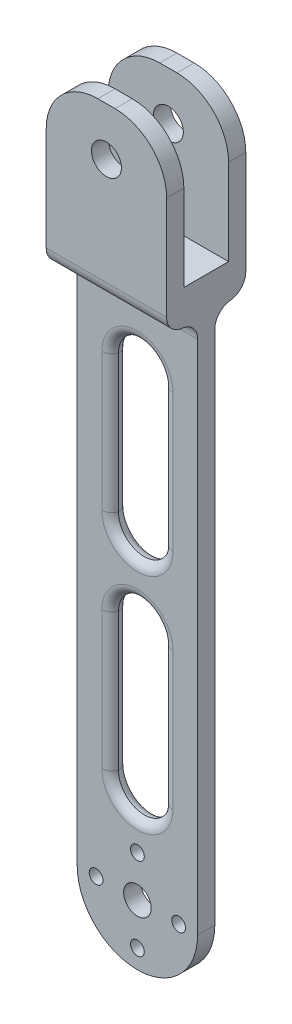
SolidWorks part; units mm, degrees
ref_plane "Front Plane" through (0, 0, 0) normal (0, 0, 1) x (1, 0, 0)
ref_plane "Top Plane" through (0, 0, 0) normal (0, 1, 0) x (1, 0, 0)
ref_plane "Right Plane" through (0, 0, 0) normal (1, 0, 0) x (0, 0, -1)
sketch "Sketch1" plane through (0, 0, 0) normal (0, 0, 1) x (1, 0, 0)
  line L0 (-9.6857, -15) -> (-9.6857, 190)
  line L1 (-9.6857, 190) -> (25.3143, 190)
  line L2 (25.3143, 190) -> (25.3143, -15)
  arc A0 (25.3143, -15) -> (-9.6857, -15) centre (7.8143, -15) cw
  circle A3 centre (19.8143, -15) radius 2
  circle A4 centre (7.8143, -27) radius 2
  circle A5 centre (-4.1857, -15) radius 2
  circle A6 centre (7.8143, -3) radius 2
  point P19 (7.8143, -15)
  dimension "D4" = 4
  dimension "D1" = 205
  dimension "D5" = 12
  dimension "D8" = 35
  dimension "D6" = 4
extrude "Boss-Extrude2" add sketch "Sketch1" along normal blind 5
sketch "Sketch3" plane through (0, 0, 5) normal (0, 0, 1) x (1, 0, 0)
  line L0 (25.3143, -15) -> (25.3143, 190) construction
  line L1 (-9.6857, 190) -> (25.3143, 190)
  line L2 (-9.6857, 190) -> (-9.6857, 140)
  line L3 (-9.6857, 140) -> (25.3143, 140)
  line L4 (25.3143, 190) -> (25.3143, 140)
  dimension "D1" = 50
extrude "Boss-Extrude3" add sketch "Sketch3" along normal blind 9 and the other way blind 14
sketch "Sketch4" plane through (25.3143, 0, 0) normal (1, 0, 0) x (0, 0, -1)
  line L0 (-14, 190) -> (9, 190) construction
  line L1 (-9, 190) -> (4, 190)
  line L2 (-9, 190) -> (-9, 150)
  line L3 (-9, 150) -> (4, 150)
  line L4 (4, 190) -> (4, 150)
  line L5 (-5, 140) -> (-14, 140) construction
  line L6 (-14, 140) -> (-14, 190) construction
  line L7 (9, 140) -> (9, 190) construction
  dimension "D1" = 10
  dimension "D2" = 5
  dimension "D3" = 5
extrude "Cut-Extrude1" cut sketch "Sketch4" against normal through all
sketch "Sketch5" plane through (0, 0, 14) normal (0, 0, 1) x (1, 0, 0)
  line L1 (25.3143, 190) -> (-9.6857, 190) construction
  circle A0 centre (7.8143, 176) radius 4.35
  dimension "D1" = 8.7
  dimension "D2" = 14
extrude "Cut-Extrude2" cut sketch "Sketch5" against normal through all
sketch "Sketch6" plane through (0, 0, 5) normal (0, 0, 1) x (1, 0, 0)
  line L0 (7.8143, 118) -> (7.8143, 78) construction
  line L1 (15.3143, 118) -> (15.3143, 78)
  line L2 (0.3143, 118) -> (0.3143, 78)
  line L4 (-9.6857, 140) -> (-9.6857, -15) construction
  line L5 (25.3143, 140) -> (-9.6857, 140) construction
  line L6 (7.8143, 53) -> (7.8143, 13) construction
  line L7 (15.3143, 53) -> (15.3143, 13)
  line L8 (0.3143, 53) -> (0.3143, 13)
  arc A0 (15.3143, 118) -> (0.3143, 118) centre (7.8143, 118) ccw
  arc A1 (0.3143, 78) -> (15.3143, 78) centre (7.8143, 78) ccw
  arc A2 (15.3143, 53) -> (0.3143, 53) centre (7.8143, 53) ccw
  arc A3 (0.3143, 13) -> (15.3143, 13) centre (7.8143, 13) ccw
  point P2 (7.8143, 98)
  point P13 (7.8143, 33)
  dimension "D5" = 25
  dimension "D1" = 17.5
  dimension "D2" = 22
  dimension "D3" = 40
  dimension "D4" = 15
  dimension "D6" = 40
  dimension "D7" = 15
extrude "Cut-Extrude3" cut sketch "Sketch6" against normal through all
fillet "Fillet14" radius 15 1 edges at (25.3143, 190, 11.5)
fillet "Fillet15" radius 15 1 edges at (-9.6857, 190, 11.5)
fillet "Fillet16" radius 15 1 edges at (-9.6857, 190, -6.5)
fillet "Fillet17" radius 15 1 edges at (25.3143, 190, -6.5)
fillet "Fillet18" radius 5 1 edges at (7.8143, 140, 5)
fillet "Fillet19" radius 5 1 edges at (7.8143, 140, 0)
fillet "Fillet20" radius 5 1 edges at (7.8143, 140, -9)
fillet "Fillet21" radius 5 1 edges at (7.8143, 140, 14)
fillet "Fillet22" radius 3 4 edges at (0.3143, 98, 0) (7.8143, 70.5, 0) (15.3143, 98, 0) (7.8143, 125.5, 0)
fillet "Fillet23" radius 3 4 edges at (15.3143, 98, 5) (7.8143, 70.5, 5) (0.3143, 98, 5) (7.8143, 125.5, 5)
fillet "Fillet24" radius 3 4 edges at (0.3143, 33, 0) (7.8143, 5.5, 0) (15.3143, 33, 0) (7.8143, 60.5, 0)
fillet "Fillet25" radius 3 4 edges at (15.3143, 33, 5) (7.8143, 5.5, 5) (0.3143, 33, 5) (7.8143, 60.5, 5)
sketch "Sketch7" plane through (0, 0, 5) normal (0, 0, 1) x (1, 0, 0)
  line L0 (-4.1857, -15) -> (19.8143, -15) construction
  line L1 (7.8143, -3) -> (7.8143, -27) construction
  circle A0 centre (7.8143, -15) radius 4
  dimension "D1" = 8
extrude "Cut-Extrude4" cut sketch "Sketch7" against normal through all
ref_plane "Plane1" through (0, 0, 2.5) normal (0, 0, -1) x (-1, 0, 0)
sketch "Sketch8" plane through (0, 0, 2.5) normal (0, 0, -1) x (-1, 0, 0)
  circle A0 centre (-7.8143, -15) radius 4 construction
  circle A1 centre (-7.8143, -15) radius 4
